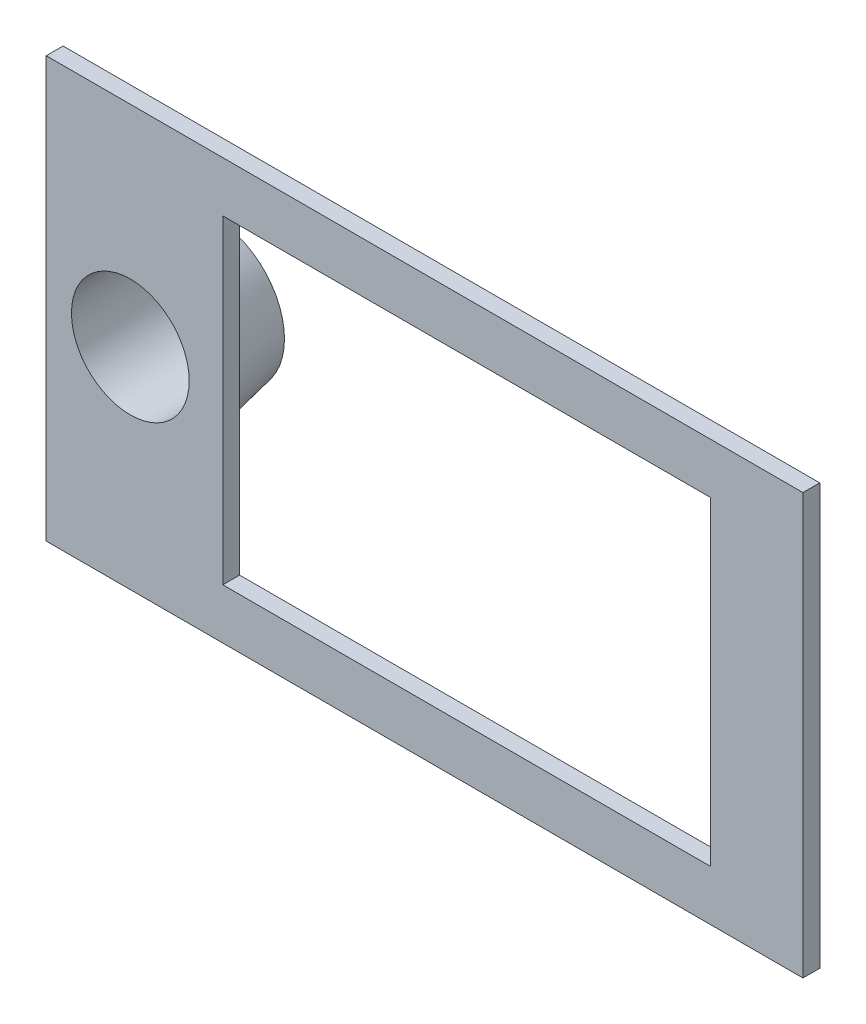
SolidWorks part; units mm, degrees
material "ABS"
ref_plane "前视基准面" through (0, 0, 0) normal (0, 0, 1) x (1, 0, 0)
ref_plane "上视基准面" through (0, 0, 0) normal (0, 1, 0) x (1, 0, 0)
ref_plane "右视基准面" through (0, 0, 0) normal (1, 0, 0) x (0, 0, -1)
sketch "草图1" plane through (0, 0, 826.3161) normal (0, 0, -1) x (-1, 0, 0)
  line L1 (-153, 72) -> (-18, 72)
  line L2 (-153, 72) -> (-153, -3)
  line L3 (-153, -3) -> (-18, -3)
  line L4 (-18, 72) -> (-18, -3)
  line L5 (-136.5, 63) -> (-49.5, 63)
  line L6 (-136.5, 63) -> (-136.5, 6)
  line L7 (-136.5, 6) -> (-49.5, 6)
  line L8 (-49.5, 63) -> (-49.5, 6)
  line L10 (-21, 0) -> (-21, 69) construction
  line L11 (-18, 72) -> (-153, 72) construction
  circle A0 centre (-33, 34.5) radius 10.5
  dimension "D1" = 21
  dimension "D2" = 3
  dimension "D3" = 12
  dimension "D4" = 28.5
  dimension "D5" = 115.5
  dimension "D6" = 132
  dimension "D7" = 9
  dimension "D8" = 37.5
  dimension "D9" = 66
  dimension "D10" = 75
extrude "凸台-拉伸1" add sketch "草图1" along normal blind 3
ref_plane "基准面4" through (0, 0, 811.3161) normal (0, 0, 1) x (1, 0, 0)
sketch "草图4" plane through (0, 0, 811.3161) normal (0, 0, 1) x (1, 0, 0)
  circle A0 centre (33, 34.5) radius 10.5
  circle A1 centre (33, 34.5) radius 12.5
  point P5 (0, 0)
  dimension "D1" = 21
  dimension "D2" = 25
  dimension "D3" = 33
  dimension "D4" = 34.5
sketch "草图5" plane through (0, 0, 823.3161) normal (0, 0, -1) x (-1, 0, 0)
  line L1 (-153, 72) -> (-153, -3) construction
  line L2 (-49.5, 63) -> (-136.5, 63) construction
  circle A0 centre (-33, 34.5) radius 10.5
  circle A1 centre (-33, 34.5) radius 15
  dimension "D1" = 21
  dimension "D2" = 30
  dimension "D3" = 120
  dimension "D4" = 28.5
loft "放样4" add section "草图5" section "草图4" connector at (33.6326, 19.5133, 823.3161) connector at (33.5463, 22.0119, 811.3161)
extrude "切除-拉伸1" cut sketch "草图5<93>" along normal up to next contours A0
sketch "草图5<93>" plane through (0, 0, 823.3161) normal (0, 0, -1) x (-1, 0, 0) same geometry as "草图5"
